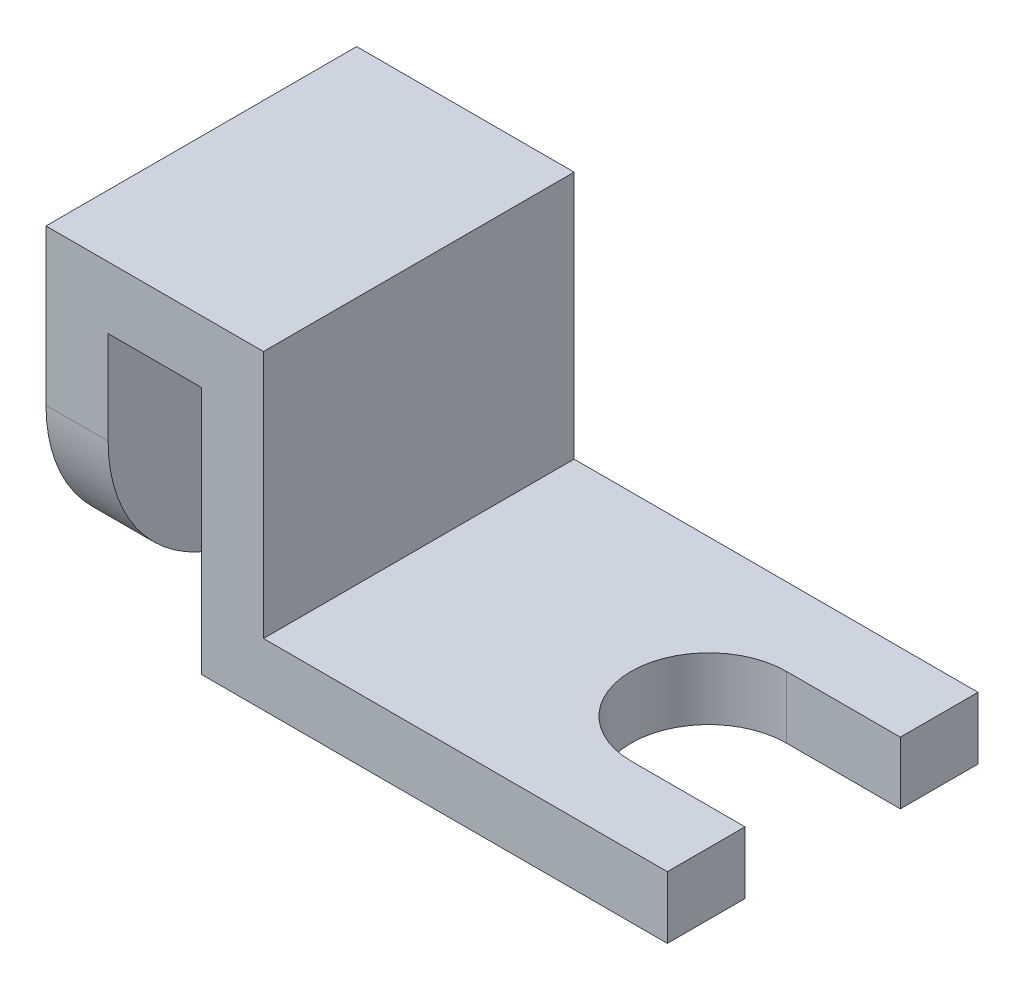
SolidWorks part; units mm, degrees
ref_plane "Спереди" through (0, 0, 0) normal (0, 0, 1) x (1, 0, 0)
ref_plane "Сверху" through (0, 0, 0) normal (0, 1, 0) x (1, 0, 0)
ref_plane "Справа" through (0, 0, 0) normal (1, 0, 0) x (0, 0, -1)
sketch "Эскиз1" plane through (0, 0, 0) normal (0, 0, 1) x (1, 0, 0)
  line L1 (-22.5, -3) -> (22.5, -3)
  line L2 (-22.5, -3) -> (-22.5, 3)
  line L3 (-22.5, 3) -> (22.5, 3)
  line L4 (22.5, -3) -> (22.5, 3)
  line L5 (-22.5, -3) -> (22.5, 3) construction
  line L6 (-22.5, 3) -> (22.5, -3) construction
  line L7 (-22.5, 3) -> (-16.5, 3)
  line L8 (-22.5, 3) -> (-22.5, 27)
  line L9 (-22.5, 27) -> (-16.5, 27)
  line L10 (-16.5, 3) -> (-16.5, 27)
  line L11 (-22.5, 27) -> (-37.5, 27)
  line L12 (-22.5, 27) -> (-22.5, 21)
  line L13 (-22.5, 21) -> (-37.5, 21)
  line L14 (-37.5, 27) -> (-37.5, 21)
  line L15 (-37.5, 21) -> (-31.5, 21)
  line L16 (-37.5, 21) -> (-37.5, -3)
  line L17 (-37.5, -3) -> (-31.5, -3)
  line L18 (-31.5, 21) -> (-31.5, -3)
  point P0 (0, 0)
  dimension "D1" = 6
  dimension "D2" = 45
  dimension "D3" = 30
  dimension "D4" = 15
extrude "Бобышка-Вытянуть1" add sketch "Эскиз1" along normal blind 30 contours L18 L13 L16 L17 | L11 L14 L13 L8 | L3 L10 L9 L8 | L1 L4 L3 L2
fillet "Скругление1" radius 15 2 edges at (-34.5, -3, 0) (-34.5, -3, 30)
sketch "Эскиз2" plane through (-37.5, 0, 0) normal (-1, 0, 0) x (0, 0, 1)
  line L0 (0, 12) -> (30, 12) construction
  circle A0 centre (15, 12) radius 6
  dimension "D1" = 12
extrude "Вырез-Вытянуть1" cut sketch "Эскиз2" against normal up to next
sketch "Эскиз3" plane through (0, 3, 0) normal (0, 1, 0) x (1, 0, 0)
  line L0 (11.5, -7.5) -> (22.5, -7.5)
  line L1 (22.5, -30) -> (22.5, 0) construction
  line L2 (22.5, -7.5) -> (22.5, -22.5)
  line L3 (22.5, -22.5) -> (11.5, -22.5)
  line L4 (22.5, -15) -> (11.5, -15) construction
  circle A0 centre (11.5, -15) radius 7.5
  dimension "D1" = 15
  dimension "D2" = 11
extrude "Вырез-Вытянуть2" cut sketch "Эскиз3" against normal through all
